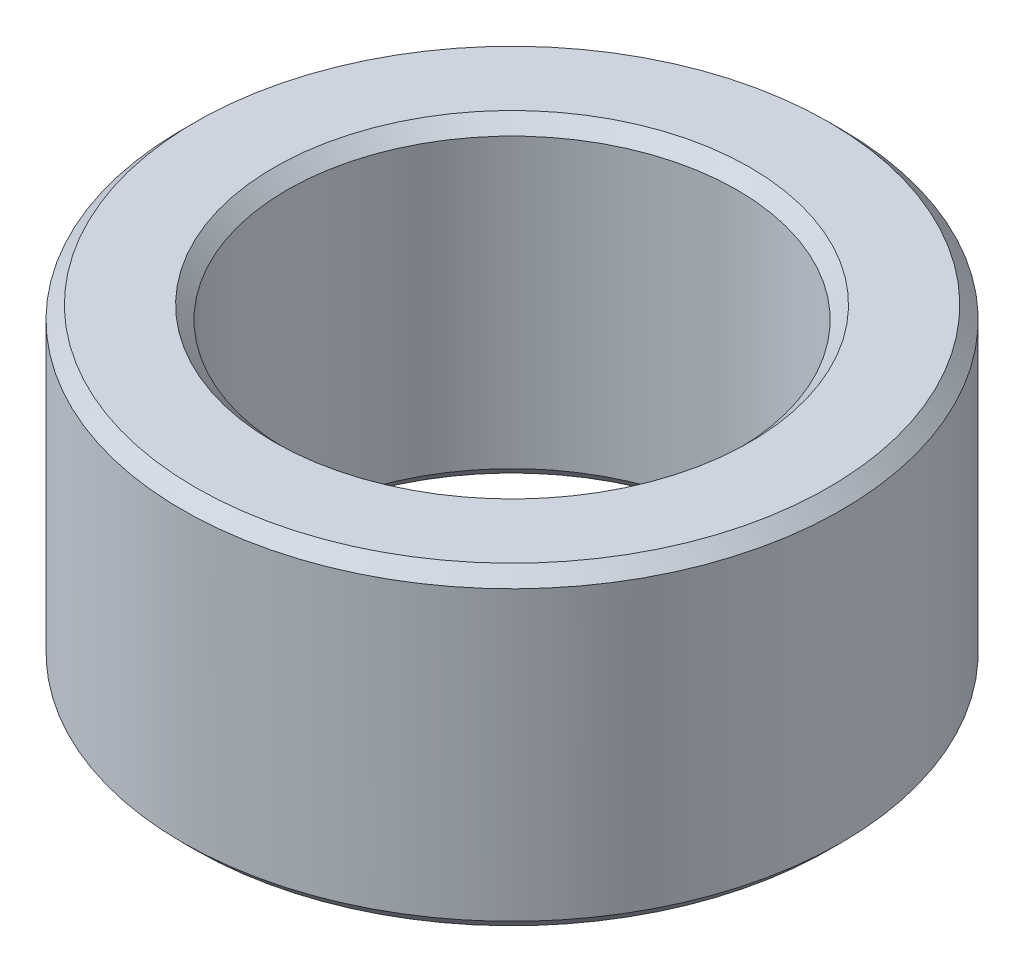
SolidWorks part; units mm, degrees
ref_plane "Front Plane" through (0, 0, 0) normal (0, 0, 1) x (1, 0, 0)
ref_plane "Top Plane" through (0, 0, 0) normal (0, 1, 0) x (1, 0, 0)
ref_plane "Right Plane" through (0, 0, 0) normal (1, 0, 0) x (0, 0, -1)
sketch "Sketch1" plane through (0, 0, 0) normal (0, 1, 0) x (1, 0, 0)
  circle A0 centre (0, 0) radius 35
  dimension "SLEEVE_OD" = 70
extrude "Boss-Extrude1" add sketch "Sketch1" along normal blind 33.3425
sketch "Sketch2" plane through (0, 0, 0) normal (0, 1, 0) x (1, 0, 0)
  circle A0 centre (0, 0) radius 23.8876
  dimension "BORE_D" = 47.7753
extrude "Cut-Extrude1" cut sketch "Sketch2" along normal through all
chamfer "Chamfer1" distance 1.3795 angle 45 4 edges at (0, 33.3425, 23.8876) (0, 0, 23.8876) (0, 0, 35) (0, 33.3425, 35)
